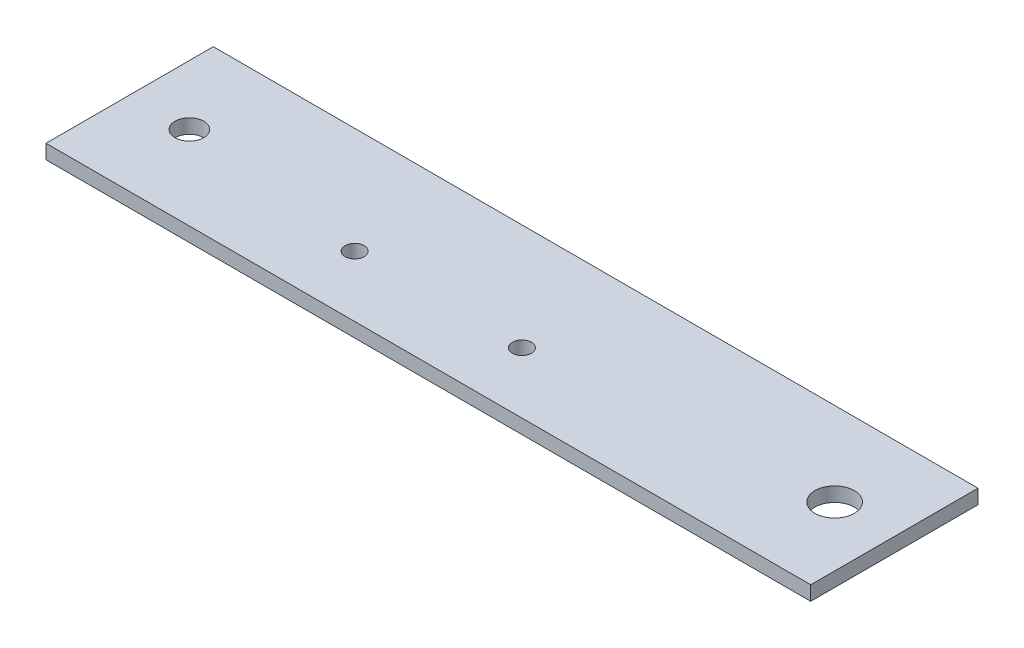
SolidWorks part; units mm, degrees
ref_plane "Front Plane" through (0, 0, 0) normal (0, 0, 1) x (1, 0, 0)
ref_plane "Top Plane" through (0, 0, 0) normal (0, 1, 0) x (1, 0, 0)
ref_plane "Right Plane" through (0, 0, 0) normal (1, 0, 0) x (0, 0, -1)
sketch "Sketch1" plane through (0, 0, 0) normal (0, 1, 0) x (1, 0, 0)
  line L1 (-80, 17.5) -> (80, 17.5)
  line L2 (-80, 17.5) -> (-80, -17.5)
  line L3 (-80, -17.5) -> (80, -17.5)
  line L4 (80, 17.5) -> (80, -17.5)
  line L5 (-80, 17.5) -> (80, -17.5) construction
  line L6 (-80, -17.5) -> (80, 17.5) construction
  circle A0 centre (-10.6801, 3.3392) radius 4.5
  circle A1 centre (-10.6585, -3.6607) radius 14
  circle A2 centre (-28.1585, -4.7634) radius 2
  circle A3 centre (6.8415, -4.7634) radius 2
  circle A4 centre (67.5, 0) radius 4.125
  point P0 (0, 0)
  point P17 (80, 0)
  dimension "D3" = 12.5
  dimension "D4" = 4
  dimension "D5" = 4
  dimension "D6" = 8.25
  dimension "D1" = 35
  dimension "D2" = 160
extrude "Boss-Extrude1" add sketch "Sketch1" along normal blind 3 contours A1 L3 L4 L1 L2 A4 A3 A2 | L3 A1 A0 | A0 region at (0, 0, -15.8622) region at (-10.656, 0, 4.4565)
sketch "Sketch2" plane through (0, 3, 0) normal (0, 1, 0) x (1, 0, 0)
  line L0 (-80, 17.5) -> (-80, -17.5) construction
  circle A0 centre (-67.5, 0) radius 3
  circle A1 centre (-67.5, 0) radius 15 construction
  circle A2 centre (-37.5, 0) radius 15 construction
  dimension "D1" = 6
  dimension "D2" = 12.5
extrude "Cut-Extrude1" cut sketch "Sketch2" against normal through all
